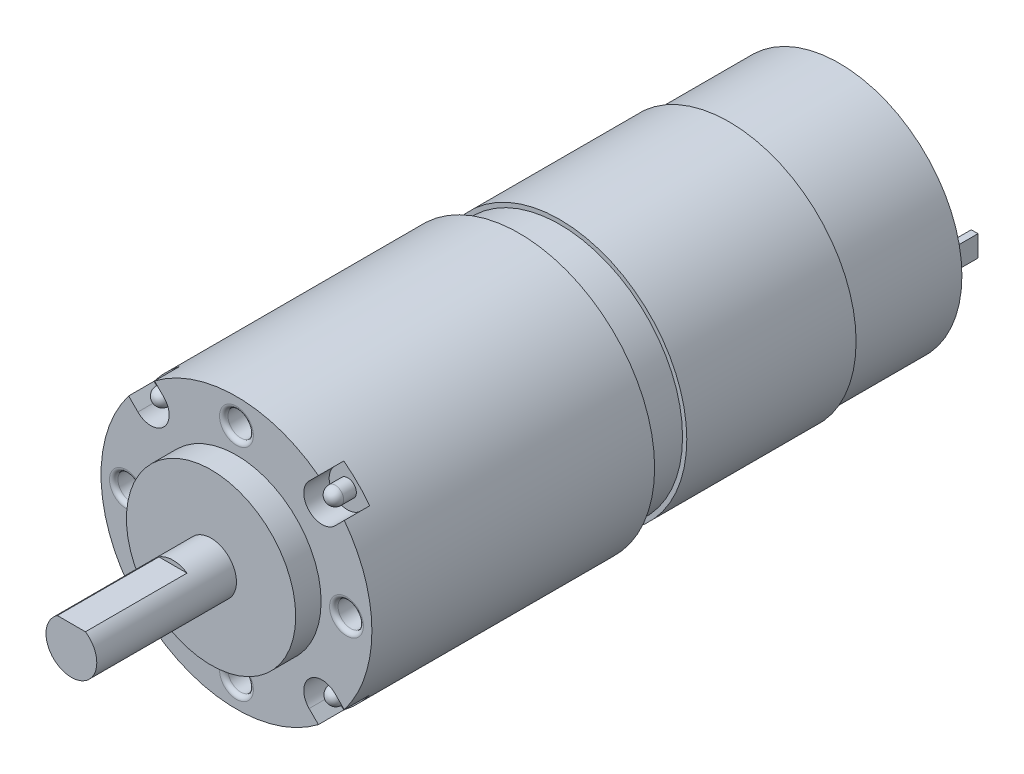
SolidWorks part; units mm, degrees
ref_plane "Plan de face" through (0, 0, 0) normal (0, 0, 1) x (1, 0, 0)
ref_plane "Plan de dessus" through (0, 0, 0) normal (0, 1, 0) x (1, 0, 0)
ref_plane "Plan de droite" through (0, 0, 0) normal (1, 0, 0) x (0, 0, -1)
sketch "Esquisse1" plane through (0, 0, 0) normal (1, 0, 0) x (0, 0, -1)
  line L0 (-20.6, 0) -> (61.7739, 0) construction
  line L1 (61.7739, 0) -> (61.7739, 3.8844)
  line L2 (61.7739, 3.8844) -> (59.7739, 3.8844)
  line L3 (59.7739, 3.8844) -> (59.7739, 14.5)
  line L4 (22.9739, 14.5) -> (26.7739, 14.5)
  line L5 (-11.4261, 16) -> (21.9739, 16)
  line L6 (-30.9261, 3) -> (-30.9261, 0)
  line L7 (21.9739, 14.5) -> (21.9739, 16)
  line L8 (21.9739, 16) -> (-11.4261, 16)
  line L9 (-11.4261, 16) -> (-11.4261, 10)
  line L10 (-11.4261, 10) -> (-14.4261, 10)
  line L11 (-14.4261, 10) -> (-14.4261, 3)
  line L12 (-14.4261, 3) -> (-30.9261, 3)
  line L13 (26.7739, 14.5) -> (26.7739, 15)
  line L14 (26.7739, 15) -> (46.7739, 15)
  line L15 (46.7739, 15) -> (46.7739, 14.5)
  line L16 (46.7739, 14.5) -> (59.7739, 14.5)
  line L17 (-30.9261, 0) -> (61.7739, 0)
  line L18 (61.7739, 0) -> (61.847, -0.5684)
  line L19 (21.9739, 13.5) -> (21.9739, 12.8615)
  line L20 (21.9739, 14.5) -> (21.9739, 13.5)
  line L21 (21.9739, 13.5) -> (21.9655, 13.4905)
  arc A0 (21.9739, 13.5) -> (22.9739, 14.5) centre (22.9739, 13.5) cw
  dimension "D8" = 1
  dimension "D1" = 15
  dimension "D2" = 10
  dimension "D3" = 16
  dimension "D4" = 14.5
  dimension "D5" = 14.5
  dimension "D6" = 20
  dimension "D7" = 13
  dimension "D9" = 3
  dimension "D10" = 16.5
  dimension "D11" = 3
  dimension "D12" = 33.4
  dimension "D13" = 2
  dimension "D14" = 37.8
revolve "Révolution1" add sketch "Esquisse1" angle 360 about L0 region at (0, 7.3186, -20.8097)
sketch "Esquisse2" plane through (0, 0, 30.9261) normal (0, 0, 1) x (1, 0, 0)
  line L0 (-1.6583, 2.5) -> (1.6583, 2.5)
  line L1 (0, 0) -> (0, 4.855) construction
  arc A0 (1.6583, 2.5) -> (-1.6583, 2.5) centre (0, 0) ccw
  point P5 (0, 2.5)
  point P7 (0, 3)
  dimension "D1" = 0.5
extrude "Enlèv. mat.-Extru.1" cut sketch "Esquisse2" against normal blind 12
sketch "Esquisse3" plane through (0, 0, -59.7739) normal (0, 0, -1) x (-1, 0, 0)
  line L0 (-12, 0) -> (11.284, 0) construction
  line L1 (0, 0) -> (0, 6.3905) construction
  line L2 (-12.4, -1.25) -> (-11.6, -1.25)
  line L3 (-12.4, -1.25) -> (-12.4, 1.25)
  line L4 (-12.4, 1.25) -> (-11.6, 1.25)
  line L5 (-11.6, -1.25) -> (-11.6, 1.25)
  line L6 (-12.4, -1.25) -> (-11.6, 1.25) construction
  line L7 (-12.4, 1.25) -> (-11.6, -1.25) construction
  line L8 (12.4, -1.25) -> (11.6, -1.25)
  line L9 (12.4, 1.25) -> (11.6, 1.25)
  line L10 (12.4, -1.25) -> (12.4, 1.25)
  line L11 (11.6, -1.25) -> (11.6, 1.25)
  dimension "D1" = 12
  dimension "D2" = 2.5
  dimension "D3" = 0.8
extrude "Boss.-Extru.1" add sketch "Esquisse3" along normal blind 4
sketch "Esquisse4" plane through (0, 0, 11.4261) normal (0, 0, 1) x (1, 0, 0)
  circle A1 centre (13, 0) radius 1.5
  circle A3 centre (0, -13) radius 1.5
  circle A5 centre (-13, 0) radius 1.5
  circle A7 centre (0, 13) radius 1.5
  point P17 (0, 0)
  dimension "D2" = 3
  dimension "D3" = 4
extrude "Enlèv. mat.-Extru.2" cut sketch "Esquisse4" against normal blind 4
fillet "Congé2" radius 0.5 4 edges at (1.5, 13, 11.4261) (-11.5, 0, 11.4261) (1.5, -13, 11.4261) (14.5, 0, 11.4261)
sketch "Esquisse5" plane through (0, 0, 11.4261) normal (0, 0, 1) x (1, 0, 0)
  line L0 (-13, 0) -> (0, 13) construction
  line L1 (0, 0) -> (-13.6057, 13.6057) construction
  line L2 (-10.1123, 10.1123) -> (-12.7098, 12.7098) construction
  line L3 (-11.6412, 8.5834) -> (-14.2388, 11.1809)
  line L4 (-8.5834, 11.6412) -> (-11.1809, 14.2388)
  line L5 (10.1123, 10.1123) -> (12.7098, 12.7098) construction
  line L6 (8.5834, 11.6412) -> (11.1809, 14.2388)
  line L7 (11.6412, 8.5834) -> (14.2388, 11.1809)
  line L8 (10.1123, -10.1123) -> (12.7098, -12.7098) construction
  line L9 (11.6412, -8.5834) -> (14.2388, -11.1809)
  line L10 (8.5834, -11.6412) -> (11.1809, -14.2388)
  line L11 (-10.1123, -10.1123) -> (-12.7098, -12.7098) construction
  line L12 (-8.5834, -11.6412) -> (-11.1809, -14.2388)
  line L13 (-11.6412, -8.5834) -> (-14.2388, -11.1809)
  arc A0 (-11.6412, 8.5834) -> (-8.5834, 11.6412) centre (-10.1123, 10.1123) ccw
  arc A1 (-11.1809, 14.2388) -> (-14.2388, 11.1809) centre (-12.7098, 12.7098) ccw
  arc A2 (8.5834, 11.6412) -> (11.6412, 8.5834) centre (10.1123, 10.1123) ccw
  arc A3 (14.2388, 11.1809) -> (11.1809, 14.2388) centre (12.7098, 12.7098) ccw
  arc A4 (11.6412, -8.5834) -> (8.5834, -11.6412) centre (10.1123, -10.1123) ccw
  arc A5 (11.1809, -14.2388) -> (14.2388, -11.1809) centre (12.7098, -12.7098) ccw
  arc A6 (-8.5834, -11.6412) -> (-11.6412, -8.5834) centre (-10.1123, -10.1123) ccw
  arc A7 (-14.2388, -11.1809) -> (-11.1809, -14.2388) centre (-12.7098, -12.7098) ccw
  point P0 (0, 13)
  point P1 (-13, 0)
  point P6 (-6.5, 6.5)
  point P12 (-11.4111, 11.4111)
  point P22 (11.4111, 11.4111)
  point P29 (11.4111, -11.4111)
  point P36 (-11.4111, -11.4111)
  point P41 (0, 0)
  dimension "D1" = 4
extrude "Enlèv. mat.-Extru.3" cut sketch "Esquisse5" against normal blind 3
sketch "Esquisse6" plane through (0, 0, 8.4261) normal (0, 0, 1) x (1, 0, 0)
  circle A0 centre (-10.2464, 10.1599) radius 1.0056
  circle A1 centre (10.1599, 10.2464) radius 1.0056
  circle A2 centre (10.2464, -10.1599) radius 1.0056
  circle A3 centre (-10.1599, -10.2464) radius 1.0056
  point P12 (0, 0)
  dimension "D1" = 4
extrude "Boss.-Extru.2" add sketch "Esquisse6" along normal blind 2.5
fillet "Congé3" radius 1 4 edges at (-9.1543, -10.2464, 10.9261) (-9.2408, 10.1599, 10.9261) (11.1655, 10.2464, 10.9261) (11.2519, -10.1599, 10.9261)
